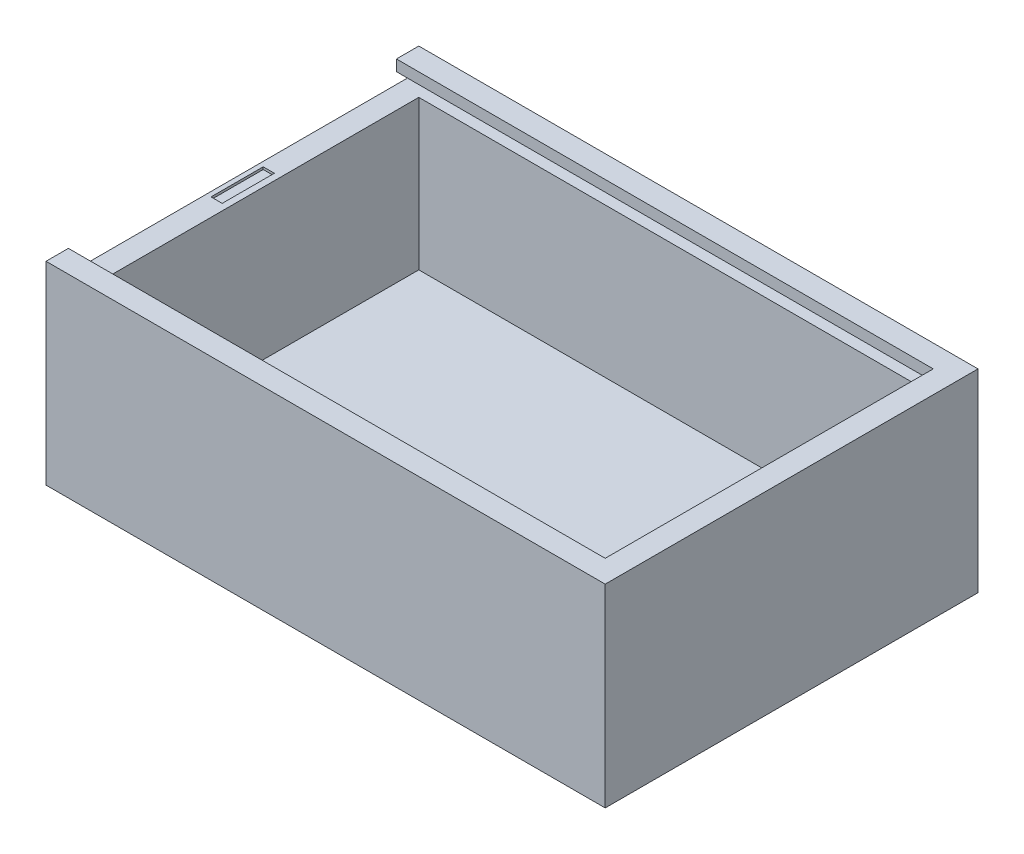
SolidWorks part; units mm, degrees
ref_plane "Front Plane" through (0, 0, 0) normal (0, 0, 1) x (1, 0, 0)
ref_plane "Top Plane" through (0, 0, 0) normal (0, 1, 0) x (1, 0, 0)
ref_plane "Right Plane" through (0, 0, 0) normal (1, 0, 0) x (0, 0, -1)
sketch "Croquis1" plane through (0, 0, 0) normal (0, 1, 0) x (1, 0, 0)
  line L0 (34.5, -22) -> (34.5, 22)
  line L1 (-37.5, 25) -> (37.5, 25)
  line L2 (-37.5, 25) -> (-37.5, -25)
  line L3 (-37.5, -25) -> (37.5, -25)
  line L4 (37.5, 25) -> (37.5, -25)
  line L5 (34.5, -22) -> (-34.5, -22)
  line L6 (34.5, 22) -> (-34.5, 22)
  line L7 (-34.5, -22) -> (-34.5, 22)
  line L8 (34.5, -22) -> (-34.5, 22) construction
  line L9 (34.5, 22) -> (-34.5, -22) construction
  point P4 (0, 25)
  point P6 (-37.5, 0)
  point P8 (0, 0)
  dimension "D1" = 75
  dimension "D2" = 50
  dimension "D3" = 3
  dimension "D4" = 3
extrude "Saliente-Extruir1" add sketch "Croquis1" along normal blind 26
extrude "Saliente-Extruir2" add sketch "Croquis1<2>" along normal blind 3 contours L7 L5 L0 L6 region at (0, 0, 0)
sketch "Croquis1<2>" plane through (0, 0, 0) normal (0, 1, 0) x (1, 0, 0) same geometry as "Croquis1"
sketch "Croquis3" plane through (-37.5, 0, 0) normal (-1, 0, 0) x (0, 0, 1)
  line L0 (-22, 26) -> (-22, 23.04)
  line L1 (-25, 26) -> (25, 26) construction
  line L2 (-22, 23.04) -> (22, 23.04)
  line L3 (22, 23.04) -> (22, 26)
  line L4 (-22, 26) -> (22, 26)
  line L5 (-25, 26) -> (-25, 0) construction
  line L6 (25, 26) -> (25, 0) construction
  line L7 (-22, 24.52) -> (-23.48, 24.52)
  line L8 (-23.48, 24.52) -> (-23.48, 23.04)
  line L9 (-23.48, 23.04) -> (-22, 23.04)
  line L10 (22, 24.52) -> (23.48, 24.52)
  line L11 (23.48, 24.52) -> (23.48, 23.04)
  line L12 (23.48, 23.04) -> (22, 23.04)
  line M7 (25, 26) -> (-25, 26)
  dimension "D1" = 3
  dimension "D2" = 3
  dimension "D3" = 1.48
  dimension "D4" = 1.48
  dimension "D5" = 1.48
extrude "Cortar-Extruir1" cut sketch "Croquis3" against normal blind 72 contours L2 L3 L0 M7 | L8 L9 L0 L7 | L12 L11 L10 L3 region at (-37.5, 24.52, 0) region at (-37.5, 23.78, -22.74) region at (-37.5, 23.78, 22.74)
sketch "Croquis4" plane through (34.5, 0, 0) normal (-1, 0, 0) x (0, 0, 1)
  line L0 (-23.48, 23.04) -> (-23.48, 24.52)
  line L1 (-23.48, 24.52) -> (23.48, 24.52)
  line L2 (23.48, 24.52) -> (23.48, 23.04)
  line L3 (23.48, 23.04) -> (-23.48, 23.04)
extrude "Cortar-Extruir2" cut sketch "Croquis4" against normal blind 1.5
sketch "Croquis7" plane through (0, 23.04, 0) normal (0, 1, 0) x (1, 0, 0)
  line L0 (-37.5, 0) -> (-34.5, 0) construction
  line L1 (-34.5, -22) -> (-34.5, 22) construction
  line L2 (-36.87, -3.5) -> (-35.37, -3.5)
  line L3 (-36.87, -3.5) -> (-36.87, 3.5)
  line L4 (-35.37, -3.5) -> (-35.37, 3.5)
  line L5 (-36.87, 3.5) -> (-35.37, 3.5)
  line L6 (-36.87, -3.5) -> (-35.37, 3.5) construction
  line L7 (-35.37, -3.5) -> (-36.87, 3.5) construction
  line L8 (-37.5, 23.48) -> (-37.5, -23.48) construction
  point P5 (-36.12, 0)
  point P6 (0, 0)
  dimension "D1" = 1.5
  dimension "D2" = 7
  dimension "D3" = 0.63
extrude "Cortar-Extruir3" cut sketch "Croquis7" against normal blind 0.32
equation "\"1.5.00mm\"=3"
